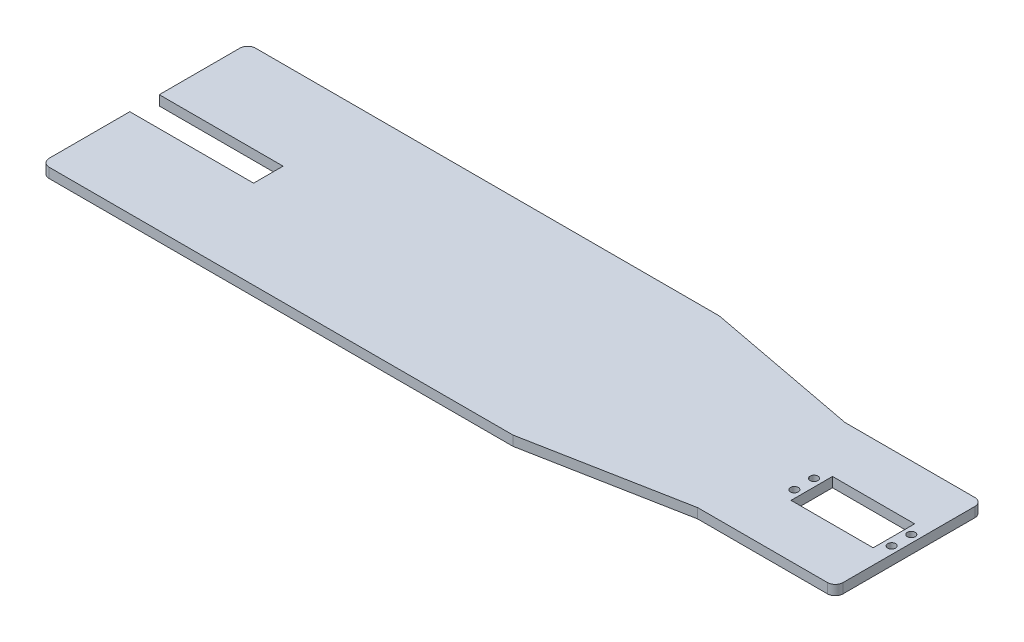
SolidWorks part; units mm, degrees
ref_plane "Front Plane" through (0, 0, 0) normal (0, 0, 1) x (1, 0, 0)
ref_plane "Top Plane" through (0, 0, 0) normal (0, 1, 0) x (1, 0, 0)
ref_plane "Right Plane" through (0, 0, 0) normal (1, 0, 0) x (0, 0, -1)
sketch "Sketch1" plane through (0, 0, 0) normal (0, 1, 0) x (1, 0, 0)
  line L0 (-120, 7.5) -> (-120, 52.5)
  line L5 (120, -52.5) -> (-120, -52.5)
  line L15 (120, 52.5) -> (-120, 52.5)
  line L16 (-120, -52.5) -> (-120, -7.5)
  line L17 (120, -52.5) -> (-120, 52.5) construction
  line L18 (120, 52.5) -> (-120, -52.5) construction
  line L19 (-120, -7.5) -> (-57, -7.5)
  line L21 (-120, 7.5) -> (-57, 7.5)
  line L22 (-57, -7.5) -> (-57, 7.5)
  line L23 (120, 52.5) -> (199, 37.5)
  line L24 (269, -37.5) -> (199, -37.5)
  line L25 (269, -37.5) -> (269, 37.5)
  line L26 (269, 37.5) -> (199, 37.5)
  line L28 (269, -37.5) -> (199, 37.5) construction
  line L29 (269, 37.5) -> (199, -37.5) construction
  line L30 (120, -52.5) -> (199, -37.5)
  line L31 (-57, 0) -> (269, 0) construction
  point P0 (0, 0)
  point P10 (234, 0)
  dimension "D3" = 63
  dimension "D1" = 240
  dimension "D2" = 105
  dimension "D4" = 15
  dimension "D5" = 45
  dimension "D6" = 70
  dimension "D7" = 75
  dimension "D8" = 79
extrude "Boss-Extrude1" add sketch "Sketch1" along normal blind 5
sketch "Sketch2" plane through (0, 5, 0) normal (0, 1, 0) x (1, 0, 0)
  line L0 (244.1396, -15.753) -> (263.6466, 47.4706) construction
  line L2 (219.55, 0) -> (261.35, 0) construction
  line L3 (261.35, 10.55) -> (261.35, -10.55)
  line L4 (261.35, 10.55) -> (219.55, 10.55)
  line L5 (219.55, 10.55) -> (219.55, -10.55)
  line L6 (261.35, -10.55) -> (219.55, -10.55)
  line L7 (265.2, 10.55) -> (265.2, -10.55) construction
  line L8 (265.2, 10.55) -> (215.7, 10.55) construction
  line L9 (215.7, 10.55) -> (215.7, -10.55) construction
  line L10 (265.2, -10.55) -> (215.7, -10.55) construction
  line L11 (269, 37.5) -> (199, 37.5) construction
  line L12 (199, -37.5) -> (269, -37.5) construction
  line L14 (269, -37.5) -> (269, 37.5) construction
  line L15 (240.45, 0) -> (240.45, 10.55) construction
  circle A0 centre (249, 0) radius 6 construction
  circle A1 centre (249, 0) radius 5.0041 construction
  circle A2 centre (265.2, 5) radius 2
  circle A3 centre (265.2, -5) radius 2
  circle A6 centre (215.7, -5) radius 2
  circle A7 centre (215.7, 5) radius 2
  point P32 (0, 0)
  dimension "D1" = 12
  dimension "D6" = 4
  dimension "D8" = 10.55
  dimension "D2" = 21.1
  dimension "D3" = 41.8
  dimension "D4" = 49.5
  dimension "D5" = 3.85
  dimension "D7" = 5
  dimension "D9" = 16.2
  dimension "D10" = 20
extrude "Cut-Extrude2" cut sketch "Sketch2" against normal blind 10
fillet "Fillet1" radius 4 4 edges at (-120, 2.5, -52.5) (-120, 2.5, 52.5) (269, 2.5, -37.5) (269, 2.5, 37.5)
